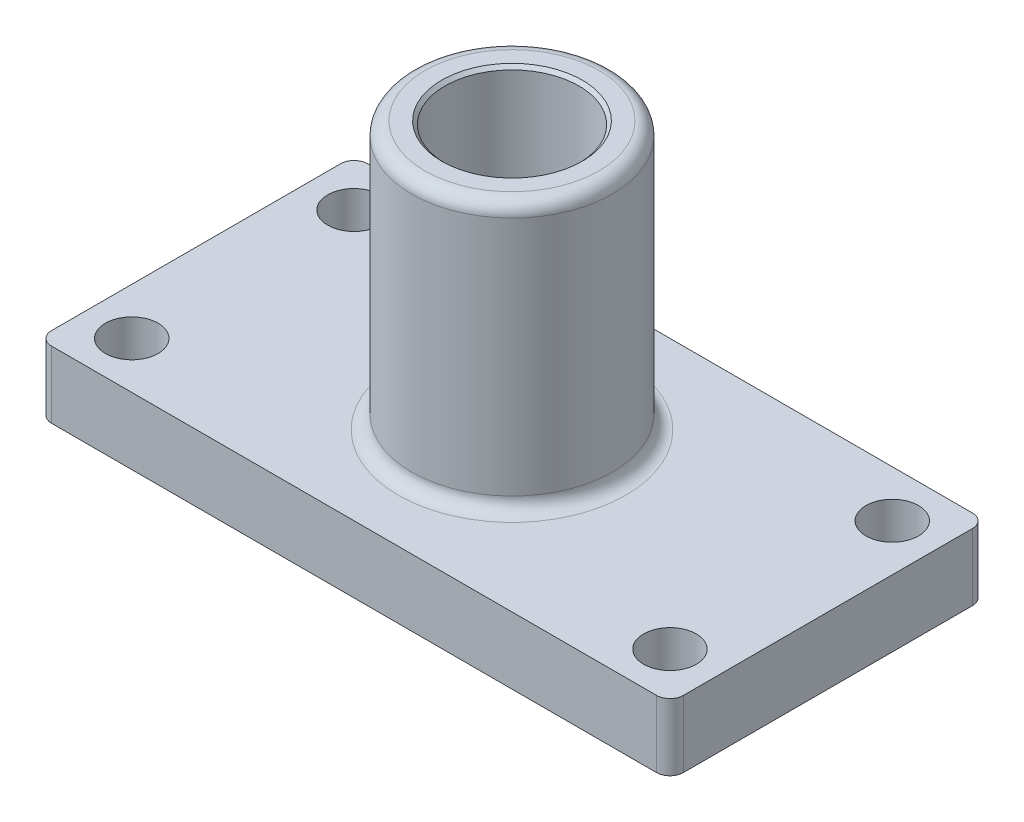
SolidWorks part; units mm, degrees
material "1060 Alloy"
ref_plane "Front Plane" through (0, 0, 0) normal (0, 0, 1) x (1, 0, 0)
ref_plane "Top Plane" through (0, 0, 0) normal (0, 1, 0) x (1, 0, 0)
ref_plane "Right Plane" through (0, 0, 0) normal (1, 0, 0) x (0, 0, -1)
sketch "Sketch1" plane through (0, 0, 0) normal (0, 1, 0) x (1, 0, 0)
  line L0 (-25.555, -10.555) -> (-25.555, 10.555)
  line L1 (-30, -15) -> (30, -15)
  line L2 (-30, -15) -> (-30, 15)
  line L3 (-30, 15) -> (30, 15)
  line L4 (30, -15) -> (30, 15)
  line L5 (-30, -15) -> (30, 15) construction
  line L6 (-30, 15) -> (30, -15) construction
  line L7 (-25.555, 10.555) -> (25.555, 10.555)
  line L8 (25.555, -10.555) -> (25.555, 10.555)
  line L9 (-25.555, -10.555) -> (25.555, -10.555)
  circle A0 centre (0, 0) radius 6.3589
  circle A1 centre (-25.555, 10.555) radius 2.5
  circle A2 centre (25.555, 10.555) radius 2.5
  circle A3 centre (25.555, -10.555) radius 2.5
  circle A4 centre (-25.555, -10.555) radius 2.5
  dimension "D3" = 12.7178
  dimension "D5" = 5
  dimension "D2" = 60
  dimension "D4" = 30
  dimension "D1" = 4.445
extrude "Boss-Extrude1" add sketch "Sketch1" along normal blind 6.35 contours L1 L4 L3 L2 A4 L0 A1 L7 A2 L8 A3 L9 | A4 L9 A3 L8 A2 L7 A1 L0 A0 region at (-25.002, 0, 0) region at (-29.3292, 0, 0)
sketch "Sketch2" plane through (0, 6.35, 0) normal (0, 1, 0) x (1, 0, 0)
  circle A0 centre (0, 0) radius 6.3589
  circle A1 centre (0, 0) radius 9.5339
  dimension "D1" = 19.0678
extrude "Boss-Extrude2" add sketch "Sketch2" along normal blind 25.4
fillet "Fillet1" radius 1.27 6 edges at (0, 31.75, 9.5339) (0, 6.35, 9.5339) (-30, 3.175, -15) (-30, 3.175, 15) (30, 3.175, -15) (30, 3.175, 15)
fillet "Chamfer5" radius 0.3175 1 edges at (0, 31.75, 6.3589) type face fillet profile chamfer first side face at (0, 31.75, 8.2639) second side face at (0, 0, 6.3589)
equation "\"Screw_hole\"= 0.5 + 0.0007"
equation "\"M5\"= 5mm"
equation "\"t\"= .25"
equation "\"w\" = .03m"
equation "\"L\"= 2 * \"w\""
equation "\"D2@Sketch1\"=\"L\""
equation "\"D3@Sketch1\"=\"Screw_hole\""
equation "\"D4@Sketch1\"=\"w\""
equation "\"D5@Sketch1\"=\"M5\""
equation "\"D1@Boss-Extrude1\"=\"t\""
equation "\"D1@Sketch2\"=\"Screw_hole\"+\"t\""
